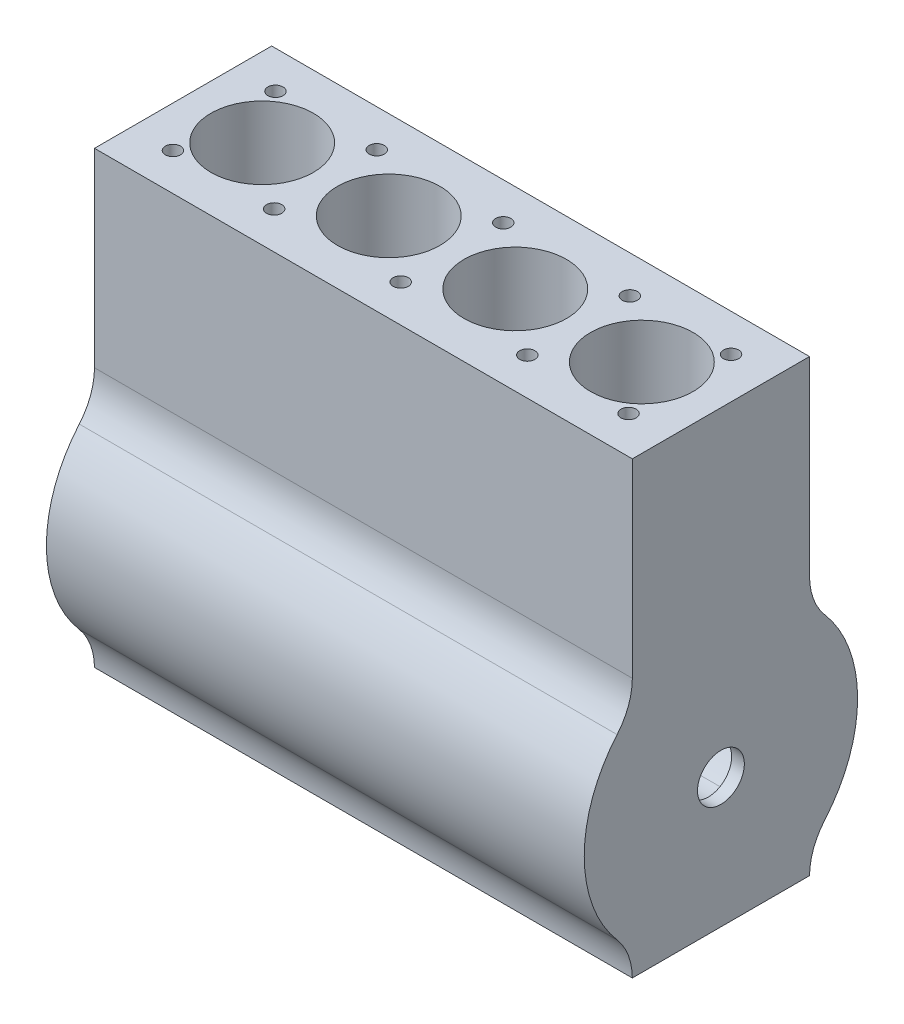
SolidWorks part; units mm, degrees
ref_plane "Front Plane" through (0, 0, 0) normal (0, 0, 1) x (1, 0, 0)
ref_plane "Top Plane" through (0, 0, 0) normal (0, 1, 0) x (1, 0, 0)
ref_plane "Right Plane" through (0, 0, 0) normal (1, 0, 0) x (0, 0, -1)
sketch "Sketch1" plane through (0, 0, 0) normal (0, 1, 0) x (1, 0, 0)
  line L0 (0, 0) -> (62.5, 0)
  line L1 (62.5, 0) -> (162.5, 0)
  line L2 (162.5, 0) -> (262.5, 0)
  line L3 (262.5, 0) -> (362.5, 0)
  line L4 (362.5, 0) -> (425, 0)
  line L5 (0, 0) -> (0, 70) construction
  line L6 (425, 0) -> (425, -70) construction
  line L8 (0, 70) -> (425, 70)
  line L9 (0, 70) -> (0, -70)
  line L10 (0, -70) -> (425, -70)
  line L11 (425, 70) -> (425, -70)
  circle A0 centre (62.5, 0) radius 40.5015
  circle A1 centre (162.5, 0) radius 40.5015
  circle A2 centre (262.5, 0) radius 40.5015
  circle A3 centre (362.5, 0) radius 40.5015
  dimension "D6" = 81.003
  dimension "D7" = 81.003
  dimension "D8" = 81.003
  dimension "D9" = 81.003
  dimension "D1" = 62.5
  dimension "D2" = 100
  dimension "D3" = 100
  dimension "D4" = 100
  dimension "D5" = 62.5
  dimension "D10" = 70
  dimension "D11" = 70
  dimension "D12" = 425
extrude "Boss-Extrude1" add sketch "Sketch1" along normal blind 350 contours A3 L3 A2 L2 A1 L1 A0 L0 L9 L10 L11 L4 | A3 L4 L11 L8 L9 L0 A0 L1 A1 L2 A2 L3 region at (212.5, 0, -44.4413) region at (212.5, 0, 44.4413)
sketch "Sketch2" plane through (0, 0, 0) normal (0, -1, 0) x (1, 0, 0)
  line L14 (415, -60) -> (415, 60)
  line L15 (10, -60) -> (415, -60)
  line L16 (10, 60) -> (10, -60)
  line L17 (415, 60) -> (10, 60)
  line L18 (415, -60) -> (415, 60)
  line L19 (10, -60) -> (415, -60)
  line L20 (10, 60) -> (10, -60)
  line L21 (415, 60) -> (10, 60)
  dimension "D1" = 10
extrude "Cut-Extrude1" cut sketch "Sketch2" against normal blind 250
sketch "Sketch3" plane through (0, 0, 0) normal (-1, 0, 0) x (0, 0, 1)
  circle A0 centre (0, 102.3197) radius 18.5
  dimension "D1" = 37
extrude "Cut-Extrude2" cut sketch "Sketch3" against normal blind 425
sketch "Sketch5" plane through (0, 0, 0) normal (-1, 0, 0) x (0, 0, 1)
  line L0 (-70, 184.5633) -> (-70, 20.0762)
  line L1 (-70, 350) -> (-70, 0) construction
  line L3 (70, 184.5633) -> (70, 20.0762)
  line L5 (70, 350) -> (70, 0) construction
  circle A0 centre (0, 102.3197) radius 108
  dimension "D1" = 216
extrude "Boss-Extrude4" add sketch "Sketch5" against normal blind 425 contours L1 A0 | A0 region at (0, 102.3197, -85.4554) region at (0, 102.3197, 85.4554)
ref_plane "Plane2" through (10, 0, 0) normal (-1, 0, 0) x (0, 0, 1)
sketch "Sketch7" plane through (10, 0, 0) normal (-1, 0, 0) x (0, 0, 1)
  circle A0 centre (0, 102.3197) radius 99
  dimension "D1" = 198
extrude "Cut-Extrude4" cut sketch "Sketch7" against normal blind 405
fillet "Fillet1" radius 20 4 edges at (212.5, 23.5733, -60) (212.5, 23.5733, 60) (212.5, 181.0661, -60) (212.5, 181.0661, 60)
fillet "Fillet2" radius 50 4 edges at (212.5, 20.0762, -70) (212.5, 20.0762, 70) (212.5, 184.5633, 70) (212.5, 184.5633, -70)
sketch "Sketch8" plane through (0, 350, 0) normal (0, 1, 0) x (1, 0, 0)
  line L0 (62.5, 40.5015) -> (362.5, 40.5015) construction
  line L1 (62.5, -40.5015) -> (362.5, -40.5015) construction
  line L2 (62.5, 0) -> (162.5, 0) construction
  line L3 (162.5, 0) -> (262.5, 0) construction
  line L4 (262.5, 0) -> (362.5, 0) construction
  line L5 (112.5, -40.5015) -> (112.5, 40.5015) construction
  line L6 (212.5, -40.5015) -> (212.5, 40.5015) construction
  line L7 (312.5, -40.5015) -> (312.5, 40.5015) construction
  line L8 (62.5, 40.5015) -> (12.5, 40.5015) construction
  line L9 (62.5, -40.5015) -> (12.5, -40.5015) construction
  line L10 (362.5, 40.5015) -> (412.5, 40.5015) construction
  line L11 (362.5, -40.5015) -> (412.5, -40.5015) construction
  line L12 (425, -82.0253) -> (425, -70) construction
  line L13 (0, 70) -> (425, 70)
  line L14 (0, 70) -> (0, -70)
  line L15 (0, -70) -> (425, -70)
  line L16 (425, 70) -> (425, -70)
  line L17 (0, -70) -> (425, -70) construction
  circle A0 centre (62.5, 0) radius 40.5015 construction
  circle A1 centre (362.5, 0) radius 40.5015 construction
  circle A2 centre (112.5, 40.5015) radius 6
  circle A3 centre (112.5, -40.5015) radius 6
  circle A4 centre (212.5, -40.5015) radius 6
  circle A5 centre (212.5, 40.5015) radius 6
  circle A6 centre (312.5, -40.5015) radius 6
  circle A7 centre (312.5, 40.5015) radius 6
  circle A8 centre (12.5, 40.5015) radius 6
  circle A9 centre (12.5, -40.5015) radius 6
  circle A10 centre (412.5, -40.5015) radius 6
  circle A11 centre (412.5, 40.5015) radius 6
  circle A12 centre (62.5, 0) radius 40.5015
  circle A13 centre (162.5, 0) radius 40.5015
  circle A14 centre (262.5, 0) radius 40.5015
  circle A15 centre (362.5, 0) radius 40.5015
  point P17 (112.5, 0)
  point P20 (212.5, 0)
  point P23 (312.5, 0)
  dimension "D4" = 12
  dimension "D5" = 12
  dimension "D6" = 12
  dimension "D7" = 12
  dimension "D8" = 12
  dimension "D9" = 12
  dimension "D14" = 12
  dimension "D15" = 12
  dimension "D16" = 12
  dimension "D17" = 12
  dimension "D1" = 100
  dimension "D2" = 100
  dimension "D3" = 100
  dimension "D10" = 50
  dimension "D11" = 50
  dimension "D12" = 50
  dimension "D13" = 50
extrude "Boss-Extrude5" add sketch "Sketch8" along normal blind 5.28
sketch "Sketch9" plane through (0, 355.28, 0) normal (0, 1, 0) x (1, 0, 0)
  line L0 (12.5, 40.5015) -> (0, 40.5015)
  line L1 (12.5, -40.5015) -> (0, -40.5015)
  line L2 (412.5, -40.5015) -> (425, -40.5015)
  line L3 (412.5, 40.5015) -> (425, 40.5015)
  line L4 (0, 70) -> (0, -70)
  line L5 (0, -70) -> (425, -70)
  line L6 (425, -70) -> (425, 70)
  line L7 (425, 70) -> (0, 70)
  line L8 (0, 70) -> (0, -70)
  line L9 (0, -70) -> (425, -70)
  line L10 (425, -70) -> (425, 70)
  line L11 (425, 70) -> (0, 70)
  line L12 (0, 40.5015) -> (32.5, 40.5015)
  line L13 (0, -40.5015) -> (32.5, -40.5015)
  line L14 (425, -40.5015) -> (392.5, -40.5015)
  line L15 (425, 40.5015) -> (392.5, 40.5015)
  circle A0 centre (32.5, 40.5015) radius 6
  circle A1 centre (32.5, -40.5015) radius 6
  circle A2 centre (392.5, -40.5015) radius 6
  circle A3 centre (392.5, 40.5015) radius 6
  circle A4 centre (112.5, 40.5015) radius 6
  circle A5 centre (112.5, -40.5015) radius 6
  circle A6 centre (212.5, -40.5015) radius 6
  circle A7 centre (212.5, 40.5015) radius 6
  circle A8 centre (312.5, 40.5015) radius 6
  circle A9 centre (312.5, -40.5015) radius 6
  circle M14 centre (312.5, -40.5015) radius 6
  circle M15 centre (212.5, -40.5015) radius 6
  circle M16 centre (112.5, 40.5015) radius 6
  circle M21 centre (112.5, -40.5015) radius 6
  circle M22 centre (212.5, 40.5015) radius 6
  circle M23 centre (312.5, 40.5015) radius 6
  dimension "D6" = 12
  dimension "D7" = 12
  dimension "D8" = 12
  dimension "D9" = 12
  dimension "D2" = 32.5
  dimension "D3" = 32.5
  dimension "D4" = 32.5
  dimension "D5" = 32.5
  dimension "D1" = 0
extrude "Cut-Extrude5" cut sketch "Sketch9" against normal blind 80 contours A0 | M16 | M22 | M15 | A1 | M21 | M14 | M23 | A3 | A2 region at (32.5, 355.28, 34.6712) region at (386.6697, 355.28, 40.5015) region at (386.6697, 355.28, -40.5015) region at (32.5, 355.28, -46.3318) region at (112.5, 355.28, -40.5015) region at (112.5, 355.28, 40.5015) region at (212.5, 355.28, 40.5015) region at (212.5, 355.28, -40.5015) region at (312.5, 355.28, -40.5015) region at (312.5, 355.28, 40.5015)
sketch "Sketch10" plane through (0, 355.28, 0) normal (0, 1, 0) x (1, 0, 0)
  circle A0 centre (12.5, 40.5015) radius 6
  circle A1 centre (12.5, -40.5015) radius 6
  circle A2 centre (412.5, -40.5015) radius 6
  circle A3 centre (412.5, 40.5015) radius 6
extrude "Boss-Extrude8" add sketch "Sketch10" against normal up to surface (5.28 mm away) up to face at (412.5, 350, 46.5015)
sketch "Sketch13" plane through (0, 250, 0) normal (0, -1, 0) x (1, 0, 0)
  line L0 (103.0015, 0) -> (121.9985, 0)
  line L1 (203.0015, 0) -> (221.9985, 0)
  line L2 (303.0015, 0) -> (321.9985, 0)
  line L3 (415, 60) -> (10, 60) construction
  line L4 (103.0015, -60) -> (121.9985, -60)
  line L5 (103.0015, -60) -> (103.0015, 60)
  line L6 (103.0015, 60) -> (121.9985, 60)
  line L7 (121.9985, -60) -> (121.9985, 60)
  line L8 (112.5, 60) -> (112.5, -60) construction
  line L9 (103.0015, 0) -> (121.9985, 0) construction
  line L11 (203.0015, -60) -> (221.9985, -60)
  line L12 (203.0015, -60) -> (203.0015, 60)
  line L13 (203.0015, 60) -> (221.9985, 60)
  line L14 (221.9985, -60) -> (221.9985, 60)
  line L15 (212.5, 60) -> (212.5, -60) construction
  line L16 (203.0015, 0) -> (221.9985, 0) construction
  line L17 (303.0015, -60) -> (321.9985, -60)
  line L18 (303.0015, -60) -> (303.0015, 60)
  line L19 (303.0015, 60) -> (321.9985, 60)
  line L20 (321.9985, -60) -> (321.9985, 60)
  line L21 (312.5, 60) -> (312.5, -60) construction
  line L22 (303.0015, 0) -> (321.9985, 0) construction
  circle A0 centre (62.5, 0) radius 40.5015 construction
  circle A1 centre (162.5, 0) radius 40.5015 construction
  circle A2 centre (262.5, 0) radius 40.5015 construction
  circle A3 centre (362.5, 0) radius 40.5015 construction
  point P17 (112.5, 0)
  point P23 (212.5, 0)
  point P27 (312.5, 0)
  line M17 (10, -60) -> (415, -60)
  line M19 (415, 60) -> (10, 60)
extrude "Boss-Extrude9" add sketch "Sketch13" along normal blind 147.68 contours L0 L7 L5 M19 | L1 L14 L12 M19 | L2 L20 L18 M19 | L7 L0 L5 M17 | L14 L1 L12 M17 | L20 L2 L18 M17 region at (112.5, 250, 30) region at (112.5, 250, -30) region at (212.5, 250, -30) region at (212.5, 250, 30) region at (312.5, 250, -30) region at (312.5, 250, 30)
sketch "Sketch14" plane through (103.0015, 0, 0) normal (-1, 0, 0) x (0, 0, 1)
  line L0 (-60, 102.32) -> (60, 102.32) construction
  circle A0 centre (0, 102.32) radius 20.5
  dimension "D1" = 41
extrude "Cut-Extrude6" cut sketch "Sketch14" against normal up to surface (218.997 mm away) up to face at (321.9985, 190.7818, 0)
sketch "Sketch15" plane through (0, 102.32, 0) normal (0, -1, 0) x (1, 0, 0)
  line L0 (103.0015, 20.5) -> (121.9985, -20.5) construction
  line L1 (121.9985, -20.5) -> (103.0015, -20.5) construction
  line L2 (103.0015, -20.5) -> (121.9985, 20.5) construction
  line L3 (121.9985, 0) -> (121.9985, 60) construction
  line L4 (103.0015, -40) -> (121.9985, -40)
  line L5 (103.0015, -40) -> (103.0015, 40)
  line L6 (103.0015, 40) -> (121.9985, 40)
  line L7 (121.9985, -40) -> (121.9985, 40)
  line L8 (112.5, 40) -> (112.5, -40) construction
  line L9 (103.0015, 0) -> (121.9985, 0) construction
  line L10 (103.0015, 20.5) -> (121.9985, 40) construction
  line L11 (121.9985, 20.5) -> (103.0015, 40) construction
  line L12 (103.0015, -20.5) -> (121.9985, -40) construction
  line L13 (103.0015, -40) -> (121.9985, -20.5) construction
  line L14 (203.0015, -40) -> (203.0015, 40)
  line L15 (203.0015, -40) -> (221.9985, -40)
  line L16 (221.9985, -40) -> (221.9985, 40)
  line L17 (203.0015, 40) -> (221.9985, 40)
  line L18 (303.0015, -40) -> (303.0015, 40)
  line L19 (303.0015, -40) -> (321.9985, -40)
  line L20 (321.9985, -40) -> (321.9985, 40)
  line L21 (303.0015, 40) -> (321.9985, 40)
  circle A0 centre (112.5, 30.25) radius 5
  circle A1 centre (112.5, -30.25) radius 5
  circle A2 centre (212.5, 30.25) radius 5
  circle A3 centre (212.5, -30.25) radius 5
  circle A4 centre (312.5, 30.25) radius 5
  circle A5 centre (312.5, -30.25) radius 5
  point P4 (112.5, 0)
  dimension "D2" = 10
  dimension "D3" = 10
  dimension "D1" = 80
  dimension "D4" = 3
extrude "Cut-Extrude7" cut sketch "Sketch15" against normal blind 50 contours A1 | A0 | A3 | A2 | A4 | A5 region at (112.5, 102.32, 30.25) region at (112.5, 102.32, -30.25) region at (212.5, 102.32, 30.25) region at (212.5, 102.32, -30.25) region at (312.5, 102.32, 30.25) region at (312.5, 102.32, -30.25)
sketch "Sketch16" plane through (0, 0, 60) normal (0, 0, 1) x (1, 0, 0)
  line L0 (221.9985, 190.4162) -> (203.0015, 190.4162)
  line L1 (203.0015, 190.4162) -> (203.0015, 102.32)
  line L2 (203.0015, 102.32) -> (221.9985, 102.32)
  line L3 (221.9985, 102.32) -> (221.9985, 190.4162)
  line L4 (121.9985, 190.4162) -> (103.0015, 190.4162)
  line L5 (103.0015, 190.4162) -> (103.0015, 102.32)
  line L6 (103.0015, 102.32) -> (121.9985, 102.32)
  line L7 (121.9985, 102.32) -> (121.9985, 190.4162)
  line L8 (121.9985, 190.4162) -> (103.0015, 190.4162)
  line L9 (103.0015, 190.4162) -> (103.0015, 102.32)
  line L10 (103.0015, 102.32) -> (121.9985, 102.32)
  line L11 (121.9985, 102.32) -> (121.9985, 190.4162)
  line L12 (321.9985, 190.4162) -> (303.0015, 190.4162)
  line L13 (303.0015, 190.4162) -> (303.0015, 102.32)
  line L14 (303.0015, 102.32) -> (321.9985, 102.32)
  line L15 (321.9985, 102.32) -> (321.9985, 190.4162)
  dimension "D1" = 0
  dimension "D2" = 3
extrude "Boss-Extrude10" add sketch "Sketch16" along normal up to surface (39 mm away) up to face at (212.5, 102.3197, 82.7773)
sketch "Sketch17" plane through (0, 0, -60) normal (0, 0, -1) x (-1, 0, 0)
  line L0 (-203.0015, 102.32) -> (-203.0015, 190.4162)
  line L1 (-203.0015, 190.4162) -> (-221.9985, 190.4162)
  line L2 (-221.9985, 190.4162) -> (-221.9985, 102.32)
  line L3 (-221.9985, 102.32) -> (-203.0015, 102.32)
  line L4 (-103.0015, 102.32) -> (-103.0015, 190.4162)
  line L5 (-103.0015, 190.4162) -> (-121.9985, 190.4162)
  line L6 (-121.9985, 190.4162) -> (-121.9985, 102.32)
  line L7 (-121.9985, 102.32) -> (-103.0015, 102.32)
  line L8 (-103.0015, 102.32) -> (-103.0015, 190.4162)
  line L9 (-103.0015, 190.4162) -> (-121.9985, 190.4162)
  line L10 (-121.9985, 190.4162) -> (-121.9985, 102.32)
  line L11 (-121.9985, 102.32) -> (-103.0015, 102.32)
  line L12 (-303.0015, 102.32) -> (-303.0015, 190.4162)
  line L13 (-303.0015, 190.4162) -> (-321.9985, 190.4162)
  line L14 (-321.9985, 190.4162) -> (-321.9985, 102.32)
  line L15 (-321.9985, 102.32) -> (-303.0015, 102.32)
  dimension "D1" = 0
  dimension "D2" = 3
extrude "Boss-Extrude11" add sketch "Sketch17" along normal blind 78
sketch "Sketch18" plane through (425, 0, 0) normal (1, 0, 0) x (0, 0, -1)
  line L0 (127.5949, 211.6062) -> (70, 211.6062)
  line L1 (127.5926, -6.9694) -> (70, 0)
  line L4 (-70, 0) -> (70, 0)
  line L5 (70, 205.101) -> (70, 355.28)
  line L6 (70, 355.28) -> (-70, 355.28)
  line L7 (-70, 355.28) -> (-70, 205.101)
  line L8 (-70, 0) -> (70, 0)
  line L9 (70, 205.101) -> (70, 355.28)
  line L10 (70, 355.28) -> (-70, 355.28)
  line L11 (-70, 355.28) -> (-70, 205.101)
  arc A0 (127.5926, -6.9694) -> (127.5949, 211.6062) centre (0, 102.3197) ccw
  arc A6 (82.0238, 32.0624) -> (70, 0) centre (119.9978, -0.4641) ccw
  arc A7 (82.0238, 32.0624) -> (82.0253, 172.5753) centre (0, 102.3197) ccw
  arc A8 (70, 205.101) -> (82.0253, 172.5753) centre (120, 205.101) ccw
  arc A9 (-82.0253, 172.5753) -> (-70, 205.101) centre (-120, 205.101) ccw
  arc A10 (-82.0253, 172.5753) -> (-82.0238, 32.0624) centre (0, 102.3197) ccw
  arc A11 (-70, 0) -> (-82.0238, 32.0624) centre (-119.9978, -0.4641) ccw
  arc A12 (82.0238, 32.0624) -> (70, 0) centre (119.9978, -0.4641) ccw
  arc A13 (82.0238, 32.0624) -> (82.0253, 172.5753) centre (0, 102.3197) ccw
  arc A14 (70, 205.101) -> (82.0253, 172.5753) centre (120, 205.101) ccw
  arc A15 (-82.0253, 172.5753) -> (-70, 205.101) centre (-120, 205.101) ccw
  arc A16 (-82.0253, 172.5753) -> (-82.0238, 32.0624) centre (0, 102.3197) ccw
  arc A17 (-70, 0) -> (-82.0238, 32.0624) centre (-119.9978, -0.4641) ccw
  arc M13 (70, 0) -> (82.0238, 32.0624) centre (119.9978, -0.4641) cw
  arc M14 (82.0238, 32.0624) -> (82.0253, 172.5753) centre (0, 102.3197) ccw
  arc M15 (82.0253, 172.5753) -> (70, 205.101) centre (120, 205.101) cw
  line M16 (70, 205.101) -> (70, 355.28)
  dimension "D1" = 0
  dimension "D2" = 60
extrude "Cut-Extrude8" cut sketch "Sketch18" against normal up to surface (425 mm away) contours L1 A0 L0 M16 M15 M14 M13 region at (425, 103.8518, -122.7429) up to face at (0, 102.3197, 18.5)
